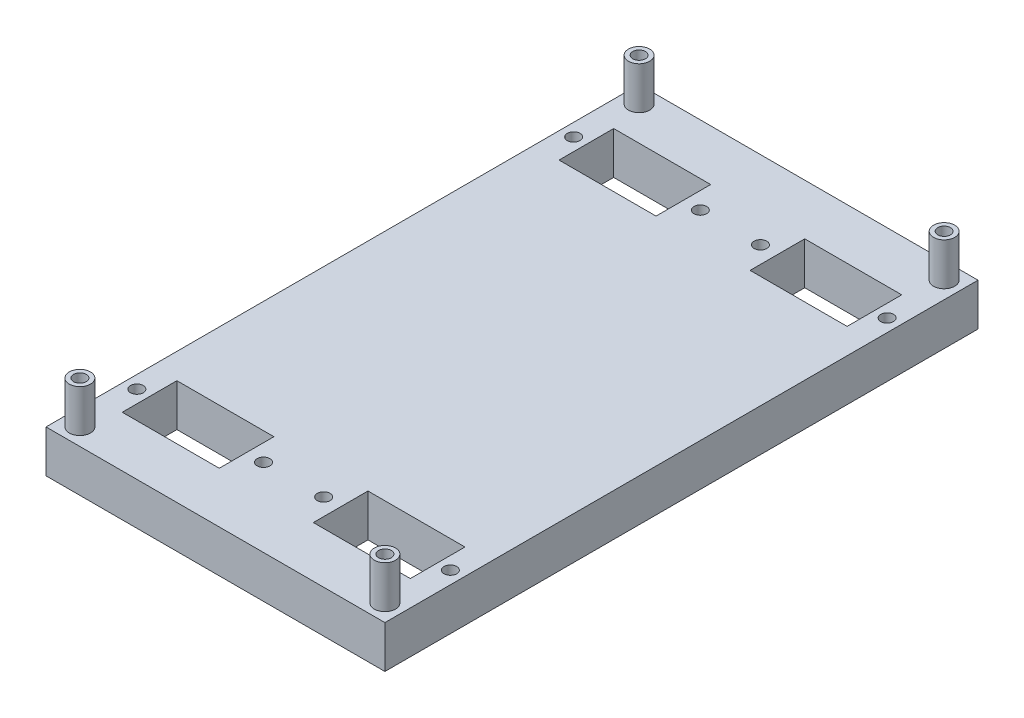
SolidWorks part; units mm, degrees
ref_plane "Front Plane" through (0, 0, 0) normal (0, 0, 1) x (1, 0, 0)
ref_plane "Top Plane" through (0, 0, 0) normal (0, 1, 0) x (1, 0, 0)
ref_plane "Right Plane" through (0, 0, 0) normal (1, 0, 0) x (0, 0, -1)
sketch "Sketch1" plane through (0, 0, 0) normal (0, 1, 0) x (1, 0, 0)
  line L1 (0, 0) -> (-80, 0)
  line L2 (0, 0) -> (0, 140)
  line L3 (0, 140) -> (-80, 140)
  line L4 (-80, 0) -> (-80, 140)
  dimension "D1" = 140
  dimension "D2" = 80
extrude "Boss-Extrude1" add sketch "Sketch1" along normal blind 10
sketch "Sketch4" plane through (0, 10, 0) normal (0, 1, 0) x (1, 0, 0)
  line L0 (0, 140) -> (-80, 140) construction
  line L1 (-6, 128) -> (-28.9, 128)
  line L2 (-6, 128) -> (-6, 115.1)
  line L3 (-6, 115.1) -> (-28.9, 115.1)
  line L4 (-28.9, 128) -> (-28.9, 115.1)
  line L5 (0, 0) -> (0, 140) construction
  dimension "D1" = 12
  dimension "D2" = 12.9
  dimension "D3" = 22.9
  dimension "D4" = 6
extrude "Cut-Extrude2" cut sketch "Sketch4" against normal through all
sketch "Sketch6" plane through (0, 10, 0) normal (0, 1, 0) x (1, 0, 0)
  line L0 (-6, 115.1) -> (-6, 128) construction
  line L1 (0, 140) -> (-80, 140) construction
  line L2 (-28.9, 128) -> (-28.9, 115.1) construction
  circle A0 centre (-3, 121.55) radius 1.5
  circle A1 centre (-32.9, 121.55) radius 1.5
  point P7 (-6, 121.55)
  point P10 (-28.9, 121.55)
  dimension "D2" = 3
  dimension "D5" = 3
  dimension "D1" = 3
  dimension "D3" = 18.45
  dimension "D4" = 18.45
  dimension "D6" = 4
extrude "Cut-Extrude4" cut sketch "Sketch6" against normal through all
ref_plane "Plane18" through (0, 0, -70) normal (0, 0, 1) x (1, 0, 0)
mirror "Mirror4" about plane through (0, 0, -70) normal (0, 0, 1) of face at (-17.45, 5, -115.1) of face at (-6, 5, -121.55) of face at (-28.9, 5, -121.55) of face at (-3, 0, -120.05) of face at (-32.9, 0, -120.05) of face at (-17.45, 5, -128)
ref_plane "Plane19" through (-40, 0, 0) normal (-1, 0, 0) x (0, 0, 1)
mirror "Mirror15" about plane through (-40, 0, 0) normal (-1, 0, 0) of "Cut-Extrude4", "Cut-Extrude2"
sketch "Sketch9" plane through (0, 10, 0) normal (0, 1, 0) x (1, 0, 0)
  line L1 (-51.1, 24.9) -> (-74, 24.9)
  line L2 (-51.1, 24.9) -> (-51.1, 12)
  line L3 (-51.1, 12) -> (-74, 12)
  line L4 (-74, 24.9) -> (-74, 12)
  line L6 (-80, 140) -> (-80, 0) construction
  line L7 (-80, 0) -> (0, 0) construction
  dimension "D1" = 12.9
  dimension "D2" = 22.9
  dimension "D3" = 6
  dimension "D4" = 12
extrude "Cut-Extrude5" cut sketch "Sketch9" against normal through all
sketch "Sketch10" plane through (0, 10, 0) normal (0, 1, 0) x (1, 0, 0)
  line L0 (-80, 0) -> (0, 0) construction
  line L1 (-51.1, 12) -> (-51.1, 24.9) construction
  circle A0 centre (-47.1, 18.45) radius 1.5
  point P4 (-51.1, 18.45)
  dimension "D1" = 3
  dimension "D2" = 18.45
  dimension "D3" = 4
extrude "Cut-Extrude6" cut sketch "Sketch10" against normal through all
sketch "Sketch11" plane through (0, 10, 0) normal (0, 1, 0) x (1, 0, 0)
  line L0 (-80, 0) -> (0, 0) construction
  line L1 (-74, 24.9) -> (-74, 12) construction
  circle A0 centre (-77, 18.45) radius 1.5
  point P4 (-74, 18.45)
  dimension "D1" = 3
  dimension "D2" = 18.45
  dimension "D3" = 3
extrude "Cut-Extrude7" cut sketch "Sketch11" against normal through all
sketch "Sketch13" plane through (0, 10, 0) normal (0, 1, 0) x (1, 0, 0)
  line L0 (0, 140) -> (-80, 140) construction
  line L1 (-80, 140) -> (-80, 0) construction
  circle A0 centre (-76, 136) radius 2.5
  dimension "D3" = 5
  dimension "D1" = 4
  dimension "D2" = 4
extrude "Boss-Extrude2" add sketch "Sketch13" along normal blind 10
sketch "Sketch14" plane through (0, 20, 0) normal (0, 1, 0) x (1, 0, 0)
  circle A0 centre (-76, 136) radius 1.5
  dimension "D1" = 3
extrude "Cut-Extrude8" cut sketch "Sketch14" against normal blind 5
sketch "Sketch15" plane through (0, 10, 0) normal (0, 1, 0) x (1, 0, 0)
  line L0 (0, 140) -> (-80, 140) construction
  line L1 (0, 0) -> (0, 140) construction
  circle A0 centre (-4, 136) radius 2.5
  dimension "D3" = 5
  dimension "D1" = 4
  dimension "D2" = 4
extrude "Boss-Extrude3" add sketch "Sketch15" along normal blind 10
sketch "Sketch16" plane through (0, 20, 0) normal (0, 1, 0) x (1, 0, 0)
  circle A0 centre (-4, 136) radius 1.5
  dimension "D1" = 3
extrude "Cut-Extrude9" cut sketch "Sketch16" against normal blind 5
mirror "Mirror22" about plane through (0, 0, -70) normal (0, 0, 1) of "Cut-Extrude9", "Boss-Extrude3", "Cut-Extrude8", "Boss-Extrude2"
